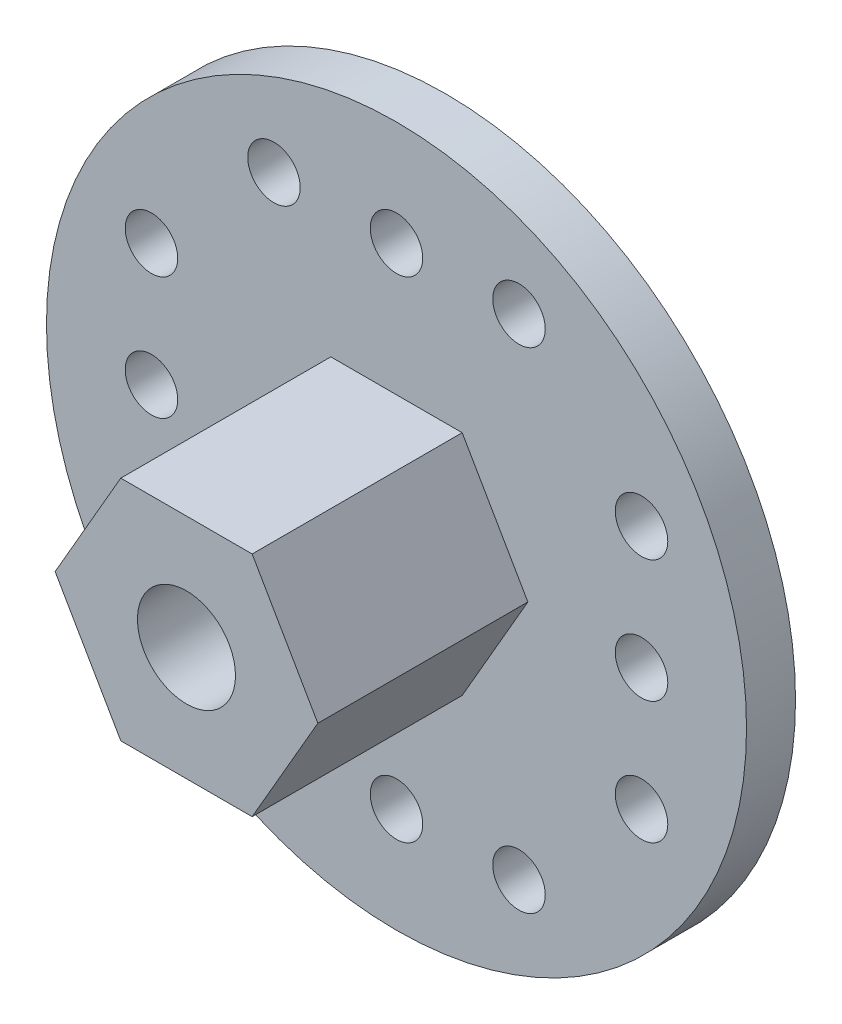
SolidWorks part; units mm, degrees
ref_plane "Front Plane" through (0, 0, 0) normal (0, 0, 1) x (1, 0, 0)
ref_plane "Top Plane" through (0, 0, 0) normal (0, 1, 0) x (1, 0, 0)
ref_plane "Right Plane" through (0, 0, 0) normal (1, 0, 0) x (0, 0, -1)
sketch "Sketch1" plane through (0, 0, 0) normal (0, 0, 1) x (1, 0, 0)
  line L0 (-6.2242, 3.1121) -> (-6.2242, -3.8879) construction
  line L1 (-6.2242, -0.3879) -> (0.7758, -0.3879) construction
  circle A0 centre (0.7758, -0.3879) radius 10
  circle A1 centre (-6.2242, -0.3879) radius 0.75
  circle A2 centre (4.2758, 6.6121) radius 0.75
  circle A3 centre (0.7758, 6.6121) radius 0.75
  circle A4 centre (-2.7242, 6.6121) radius 0.75
  circle A5 centre (7.7758, -3.8879) radius 0.75
  circle A6 centre (7.7758, -0.3879) radius 0.75
  circle A7 centre (7.7758, 3.1121) radius 0.75
  circle A8 centre (-2.7242, -7.3879) radius 0.75
  circle A9 centre (0.7758, -7.3879) radius 0.75
  circle A10 centre (4.2758, -7.3879) radius 0.75
  circle A11 centre (-6.2242, -3.8879) radius 0.75
  circle A12 centre (-6.2242, 3.1121) radius 0.75
  point P22 (0.7758, -0.3879)
  dimension "D2" = 20
  dimension "D3" = 1.5
  dimension "D4" = 7
  dimension "D5" = 3.5
  dimension "D6" = 3.5
extrude "Boss-Extrude1" add sketch "Sketch1" along normal blind 1.4
sketch "Sketch2" plane through (0, 0, 1.4) normal (0, 0, 1) x (1, 0, 0)
  line L0 (-9.2242, -0.3879) -> (10.7758, -0.3879) construction
  line L1 (0.7758, -10.3879) -> (0.7758, 9.6121) construction
  line L3 (4.5286, -0.3879) -> (2.6522, 2.8621)
  line L4 (2.6522, 2.8621) -> (-1.1005, 2.8621)
  line L5 (-1.1005, 2.8621) -> (-2.9769, -0.3879)
  line L6 (-2.9769, -0.3879) -> (-1.1005, -3.6379)
  line L7 (-1.1005, -3.6379) -> (2.6522, -3.6379)
  line L8 (2.6522, -3.6379) -> (4.5286, -0.3879)
  circle A0 centre (0.7758, -0.3879) radius 10 construction
  circle A1 centre (0.7758, -0.3879) radius 3.25 construction
  dimension "D1" = 6.5
extrude "Boss-Extrude2" add sketch "Sketch2" along normal blind 6
sketch "Sketch3" plane through (0, 0, 0) normal (0, 0, -1) x (-1, 0, 0)
  circle A0 centre (-0.7758, -0.3879) radius 3.25
  dimension "D1" = 6.5
extrude "Cut-Extrude1" cut sketch "Sketch3" against normal blind 0.4
sketch "Sketch4" plane through (0, 0, 7.4) normal (0, 0, 1) x (1, 0, 0)
  line L0 (3.5904, 1.2371) -> (-2.0387, -2.0129) construction
  line L1 (4.5286, -0.3879) -> (2.6522, 2.8621) construction
  line L2 (-2.9769, -0.3879) -> (-1.1005, -3.6379) construction
  line L3 (-1.1005, 2.8621) -> (2.6522, -3.6379) construction
  circle A0 centre (0.7758, -0.3879) radius 1.4
  dimension "D1" = 2.8
extrude "Cut-Extrude2" cut sketch "Sketch4" against normal blind 5
